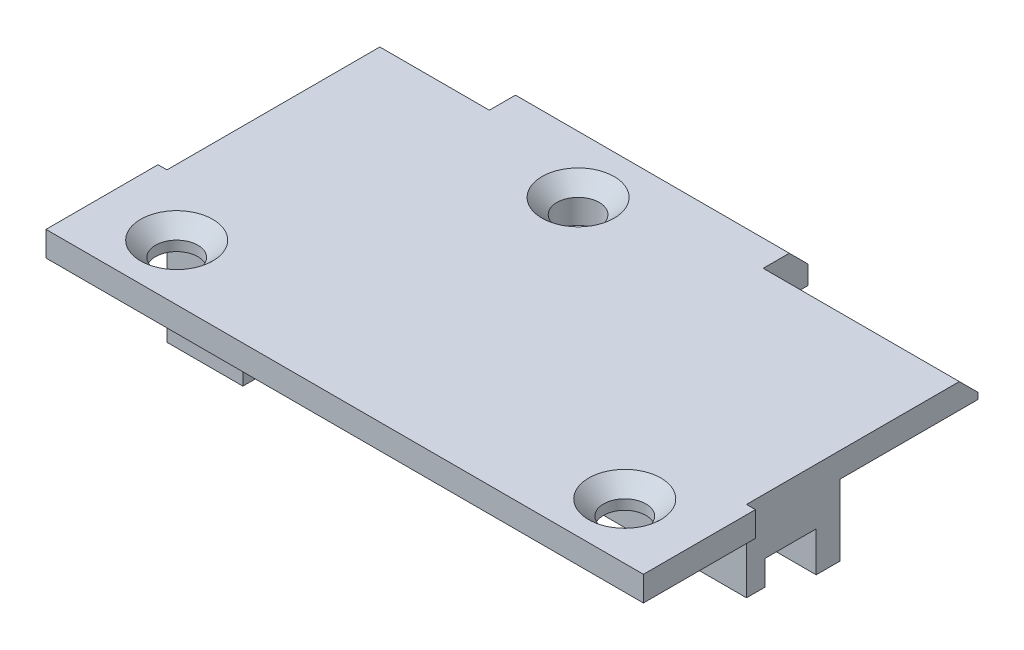
SolidWorks part; units mm, degrees
ref_plane "Front Plane" through (0, 0, 0) normal (0, 0, 1) x (1, 0, 0)
ref_plane "Top Plane" through (0, 0, 0) normal (0, 1, 0) x (1, 0, 0)
ref_plane "Right Plane" through (0, 0, 0) normal (1, 0, 0) x (0, 0, -1)
sketch "Sketch1" plane through (0, 0, 0) normal (0, 1, 0) x (1, 0, 0)
  line L0 (0, 0) -> (0, 9)
  line L1 (0, 9) -> (0.72, 9)
  line L2 (0.72, 9) -> (0.72, 27.6)
  line L3 (0.72, 27.6) -> (9.52, 27.6)
  line L4 (9.52, 27.6) -> (9.52, 29.7)
  line L5 (9.52, 29.7) -> (31.52, 29.7)
  line L6 (31.52, 29.7) -> (31.52, 27.6)
  line L7 (31.52, 27.6) -> (47.28, 27.6)
  line L8 (47.28, 27.6) -> (47.28, 9)
  line L9 (47.28, 9) -> (48, 9)
  line L10 (48, 9) -> (48, 0)
  line L11 (48, 0) -> (0, 0)
  circle A0 centre (19.15, 23.6) radius 1.7
  circle A1 centre (6, 4.5) radius 1.7
  circle A2 centre (42, 4.5) radius 1.7
  dimension "D8" = 3.4
  dimension "D1" = 48
  dimension "D2" = 9
  dimension "D3" = 0.72
  dimension "D4" = 18.6
  dimension "D5" = 2.1
  dimension "D6" = 22
  dimension "D7" = 15.76
  dimension "D9" = 23.6
  dimension "D10" = 18.43
  dimension "D11" = 4.5
  dimension "D12" = 6
  dimension "D13" = 6
  dimension "D14" = 4.5
extrude "Boss-Extrude1" add sketch "Sketch1" against normal blind 2
chamfer "Chamfer1" distance 1.5 angle 45 3 edges at (5.12, 0, -27.6) (20.52, 0, -29.7) (39.4, 0, -27.6)
chamfer "Chamfer2" distance 1.2 angle 45 3 edges at (6, 0, -2.8) (19.15, 0, -21.9) (42, 0, -2.8)
sketch "Sketch2" plane through (0, -2, 0) normal (0, -1, 0) x (1, 0, 0)
  line L1 (9.52, -29.7) -> (31.52, -29.7)
  line L2 (9.52, -29.7) -> (9.52, -27.6)
  line L3 (9.52, -27.6) -> (31.52, -27.6)
  line L4 (31.52, -29.7) -> (31.52, -27.6)
extrude "Boss-Extrude2" add sketch "Sketch2" along normal blind 1
sketch "Sketch3" plane through (0, -2, 0) normal (0, -1, 0) x (1, 0, 0)
  line L0 (31.52, -27.6) -> (9.52, -27.6) construction
  line L1 (11.72, -27.6) -> (26.28, -27.6)
  line L2 (11.72, -27.6) -> (11.72, -19.6)
  line L3 (11.72, -19.6) -> (26.28, -19.6)
  line L4 (26.28, -27.6) -> (26.28, -19.6)
  line L5 (0.72, -27.6) -> (0.72, -9) construction
  circle A0 centre (19.15, -23.6) radius 1.7
  circle A1 centre (19.15, -23.6) radius 1.7 construction
  dimension "D1" = 11
  dimension "D2" = 14.56
  dimension "D3" = 8
extrude "Boss-Extrude3" add sketch "Sketch3" along normal blind 1.15
sketch "Sketch4" plane through (0, -2, 0) normal (0, -1, 0) x (1, 0, 0)
  line L0 (0.72, -9) -> (47.28, -9)
  line L1 (47.28, -9) -> (47.28, -16.5)
  line L2 (47.28, -9) -> (47.28, -27.6) construction
  line L3 (47.28, -16.5) -> (44.18, -16.5)
  line L4 (44.18, -16.5) -> (44.18, -18.4)
  line L5 (44.18, -18.4) -> (42.26, -18.4)
  line L6 (42.26, -18.4) -> (42.26, -16.5)
  line L7 (42.26, -16.5) -> (38.56, -16.5)
  line L8 (38.56, -16.5) -> (38.56, -18.4)
  line L9 (38.56, -18.4) -> (35.18, -18.4)
  line L10 (35.18, -18.4) -> (35.18, -16.5)
  line L11 (35.18, -16.5) -> (31.48, -16.5)
  line L12 (31.48, -16.5) -> (31.48, -18.4)
  line L13 (31.48, -18.4) -> (30.09, -18.4)
  line L14 (30.09, -18.4) -> (30.09, -14.6)
  line L15 (30.09, -14.6) -> (26.6, -14.6)
  line L16 (26.6, -14.6) -> (26.6, -13.6)
  line L17 (26.6, -13.6) -> (11.4, -13.6)
  line L18 (11.4, -13.6) -> (11.4, -18.4)
  line L19 (11.4, -18.4) -> (10.02, -18.4)
  line L20 (10.02, -18.4) -> (10.02, -16.5)
  line L21 (10.02, -16.5) -> (6.32, -16.5)
  line L22 (6.32, -16.5) -> (6.32, -18.4)
  line L23 (6.32, -18.4) -> (3.72, -18.4)
  line L24 (3.72, -18.4) -> (3.72, -19.6)
  line L25 (3.72, -19.6) -> (0.72, -19.6)
  line L26 (0.72, -27.6) -> (0.72, -9) construction
  line L27 (0.72, -19.6) -> (0.72, -9)
  dimension "D1" = 3
  dimension "D2" = 2.6
  dimension "D3" = 3.7
  dimension "D4" = 1.38
  dimension "D5" = 15.2
  dimension "D6" = 3.49
  dimension "D7" = 3.7
  dimension "D8" = 3.7
  dimension "D9" = 3.1
  dimension "D10" = 1.39
  dimension "D11" = 3.38
  dimension "D12" = 7.5
  dimension "D13" = 1.9
  dimension "D14" = 3.8
  dimension "D15" = 1
  dimension "D16" = 4.8
  dimension "D17" = 1.9
  dimension "D18" = 1.2
extrude "Boss-Extrude4" add sketch "Sketch4" along normal blind 5.7
fillet "Fillet1" radius 0.5 12 edges at (42.26, -4.85, -18.4) (42.26, -4.85, -16.5) (35.18, -4.85, -18.4) (35.18, -4.85, -16.5) (38.56, -4.85, -16.5) (38.56, -4.85, -18.4) (31.48, -4.85, -16.5) (31.48, -4.85, -18.4) (10.02, -4.85, -18.4) (10.02, -4.85, -16.5) (6.32, -4.85, -16.5) (6.32, -4.85, -18.4)
sketch "Sketch5" plane through (0, -7.7, 0) normal (0, -1, 0) x (1, 0, 0)
  line L1 (0.72, -9) -> (6.82, -9)
  line L2 (0.72, -9) -> (0.72, -14.6)
  line L3 (0.72, -14.6) -> (6.82, -14.6)
  line L4 (6.82, -9) -> (6.82, -14.6)
  dimension "D1" = 5.6
  dimension "D2" = 6.1
extrude "Boss-Extrude5" add sketch "Sketch5" along normal blind 4.3
sketch "Sketch6" plane through (0, -7.7, 0) normal (0, -1, 0) x (1, 0, 0)
  line L0 (47.28, -16.5) -> (47.28, -9) construction
  line L1 (6.82, -9) -> (47.28, -9)
  line L2 (6.82, -9) -> (6.82, -14.6)
  line L3 (6.82, -14.6) -> (47.28, -14.6)
  line L4 (47.28, -9) -> (47.28, -14.6)
  line L5 (0.72, -14.6) -> (6.82, -14.6) construction
extrude "Cut-Extrude1" cut sketch "Sketch6" against normal blind 1.2
sketch "Sketch7" plane through (0, -6.5, 0) normal (0, -1, 0) x (1, 0, 0)
  line L0 (11.4, -13.6) -> (11.4, -13.32)
  line L1 (12.14, -12.35) -> (14.52, -11.6893)
  line L2 (23.64, -10.5) -> (47.28, -10.5)
  line L3 (47.28, -14.6) -> (47.28, -9) construction
  line L4 (47.28, -10.5) -> (47.28, -14.6)
  line L5 (47.28, -14.6) -> (26.6, -14.6)
  line L6 (26.6, -14.6) -> (26.6, -13.6)
  line L7 (26.6, -13.6) -> (11.4, -13.6)
  arc A0 (11.4, -13.32) -> (12.14, -12.35) centre (12.4, -13.3156) cw
  arc A1 (14.52, -11.6893) -> (23.64, -10.5) centre (23.5667, -45.4999) cw
  point P17 (15.6494, -10.963)
  point P18 (13.0341, -11.1968)
  point P19 (12.4, -12.35)
  dimension "D5" = 1
  dimension "D6" = 35
  dimension "D1" = 23.64
  dimension "D2" = 4.1
  dimension "D3" = 0.28
  dimension "D4" = 2.47
  dimension "D7" = 0.97
  dimension "D8" = 0.74
  dimension "D9" = 2.38
extrude "Cut-Extrude2" cut sketch "Sketch7" against normal blind 2
